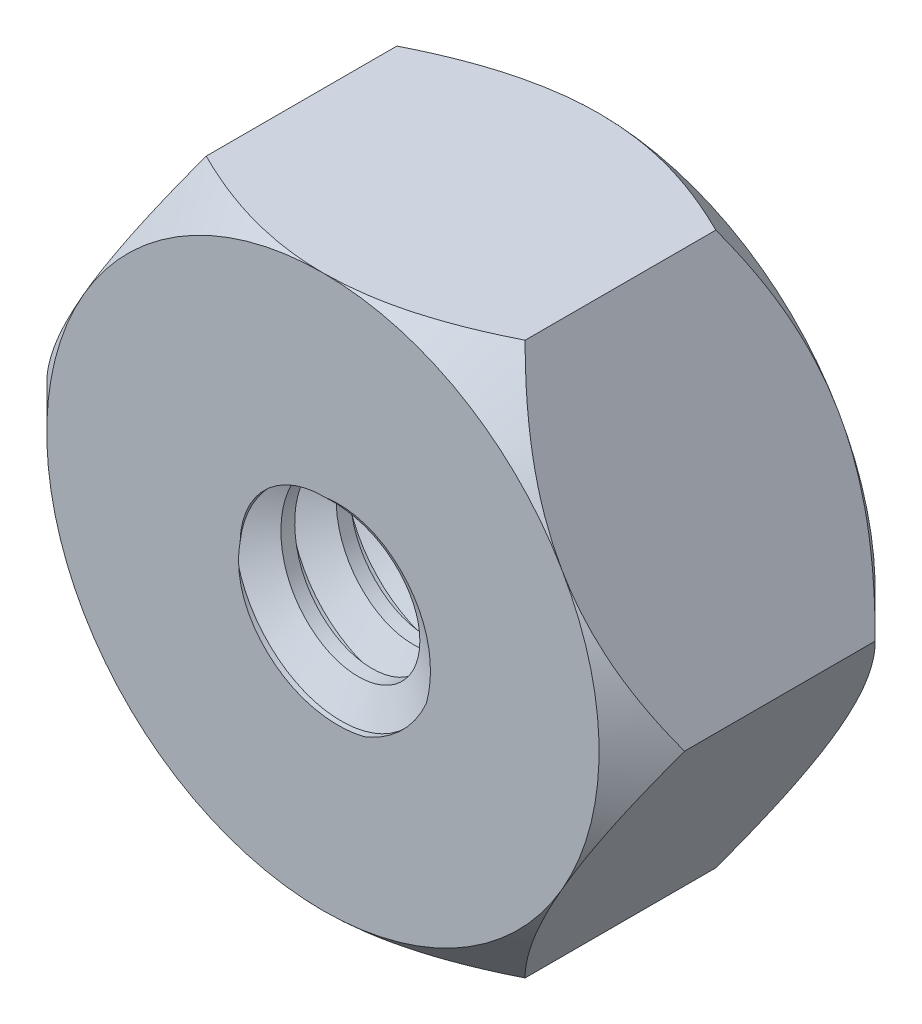
SolidWorks part; units mm, degrees
ref_plane "Front Plane" through (0, 0, 0) normal (0, 0, 1) x (1, 0, 0)
ref_plane "Top Plane" through (0, 0, 0) normal (0, 1, 0) x (1, 0, 0)
ref_plane "Right Plane" through (0, 0, 0) normal (1, 0, 0) x (0, 0, -1)
sketch "Sketch1" plane through (0, 0, 0) normal (0, 0, 1) x (1, 0, 0)
  line L1 (5.7735, 0) -> (2.8868, 5)
  line L2 (2.8868, 5) -> (-2.8868, 5)
  line L3 (-2.8868, 5) -> (-5.7735, 0)
  line L4 (-5.7735, 0) -> (-2.8868, -5)
  line L5 (-2.8868, -5) -> (2.8868, -5)
  line L6 (2.8868, -5) -> (5.7735, 0)
  circle A0 centre (0, 0) radius 5 construction
  circle A1 centre (0, 0) radius 2
  dimension "D1" = 10
  dimension "D2" = 4
extrude "Boss-Extrude2" add sketch "Sketch1" along normal mid plane 5 contours A1 | L5 L6 L1 L2 L3 L4 A1 region at (4.1978, -2.4236, 0) region at (0, 0, 0)
sketch "Sketch3" plane through (0, 0, 2.5) normal (0, 0, 1) x (1, 0, 0)
  circle A0 centre (0, 0) radius 1.5
sketch "Sketch4" plane through (0, 0, 2.5) normal (0, 0, 1) x (1, 0, 0)
  circle A0 centre (0, 0) radius 5
extrude "Cut-Extrude1" cut sketch "Sketch4" against normal blind 37.5 draft 45 flip side to cut
mirror "Mirror1" about plane through (0, 0, 0) normal (0, 0, 1) of "Cut-Extrude1"
extrude "Cut-Extrude4" cut sketch "Sketch3" against normal through all contours A0
thread "Thread2" pitch 1 method cut profile "Thread Profile2" start angle 1, offset 1, length 6, pitch 1, diameter 3
ref_plane "Plane2" through (-1.4998, 0.0262, 3.5) normal (-0.0175, -0.9998, 0) x (-0.9998, 0.0175, 0)
sketch "Thread Profile2" plane through (-1.4998, 0.0262, 3.5) normal (-0.0175, -0.9998, 0) x (-0.9998, 0.0175, 0)
  line L0 (0, 0) -> (0, 1) construction
  line L1 (0, 0) -> (0.5413, 0.3125)
  line L2 (0.5413, 0.3125) -> (0.5413, 0.4375)
  line L3 (0.5413, 0.4375) -> (0, 0.75)
  line L4 (0.5413, 0.375) -> (0, 0.375) construction
  line L11 (0, 0) -> (0, 0.75)
  point P2 (0, 0)
  dimension "Pitch" = 1
  dimension "Profile_Angle" = 60
  dimension "Profile_Land" = 0.125
  dimension "Profile_Height" = 0.5413
sketch "Sketch5" plane through (0, 0, 0) normal (0, 0, 1) x (1, 0, 0)
  circle A0 centre (0, 0) radius 0.6
